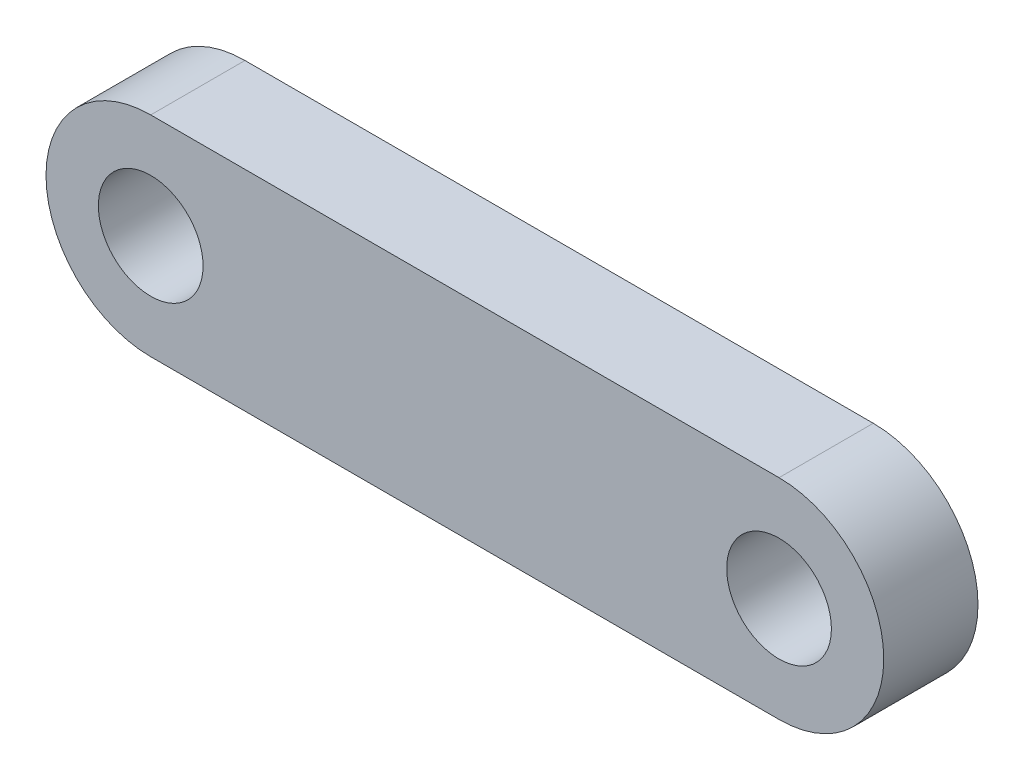
SolidWorks part; units mm, degrees
material "ABS"
ref_plane "Front Plane" through (0, 0, 0) normal (0, 0, 1) x (1, 0, 0)
ref_plane "Top Plane" through (0, 0, 0) normal (0, 1, 0) x (1, 0, 0)
ref_plane "Right Plane" through (0, 0, 0) normal (1, 0, 0) x (0, 0, -1)
ref_axis "X" through (-88.99, 0, 0) along (1, 0, 0)
ref_axis "Y" through (0, 55, 0) along (0, -1, 0)
ref_axis "Z" through (0, 0, -88.99) along (0, 0, 1)
sketch "Sketch1" plane through (0, 0, 0) normal (0, 0, 1) x (1, 0, 0)
  line L0 (-30, 0) -> (30, 0) construction
  line L1 (-30, 10) -> (30, 10)
  line L2 (-30, -10) -> (30, -10)
  arc A0 (-30, 10) -> (-30, -10) centre (-30, 0) ccw
  arc A1 (30, -10) -> (30, 10) centre (30, 0) ccw
  circle A2 centre (-30, 0) radius 5
  circle A3 centre (30, 0) radius 5
  point P2 (0, 0)
  dimension "D1" = 5
  dimension "D3" = 10
  dimension "D2" = 60
extrude "Boss-Extrude1" add sketch "Sketch1" along normal mid plane 9
